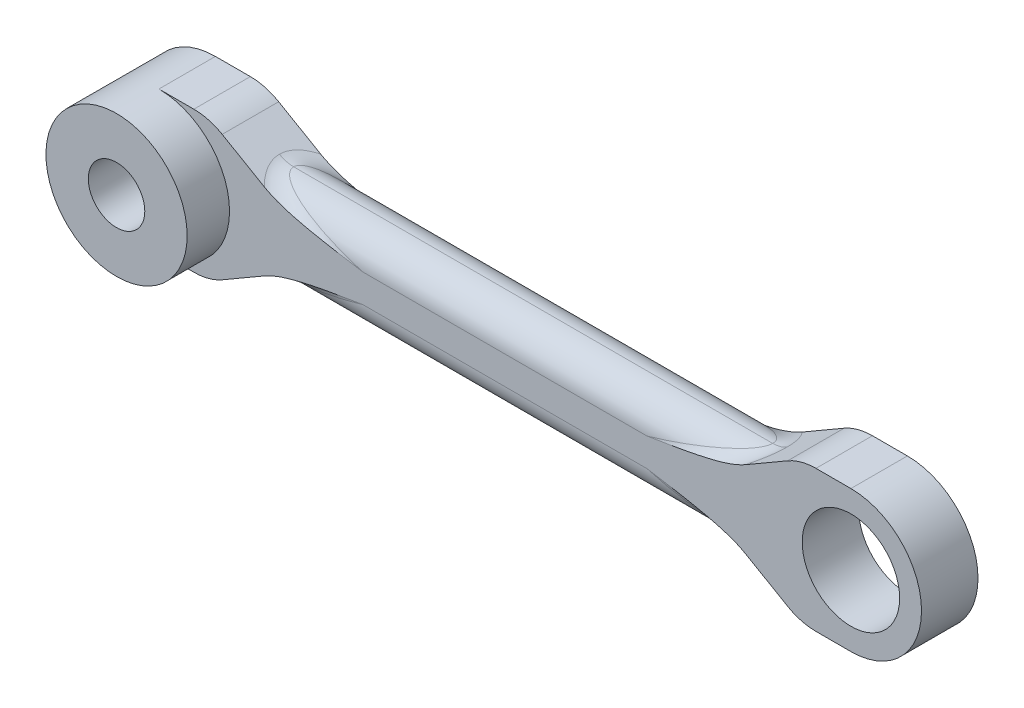
SolidWorks part; units mm, degrees
ref_plane "Ön Düzlem" through (0, 0, 0) normal (0, 0, 1) x (1, 0, 0)
ref_plane "Üst Düzlem" through (0, 0, 0) normal (0, 1, 0) x (1, 0, 0)
ref_plane "Sağ Düzlem" through (0, 0, 0) normal (1, 0, 0) x (0, 0, -1)
sketch "Çizim1" plane through (0, 0, 0) normal (0, 0, 1) x (1, 0, 0)
  line L0 (0, 5) -> (49, 5)
  line L1 (0, -5) -> (49, -5)
  circle A0 centre (0, 0) radius 5
  circle A1 centre (0, 0) radius 3.45
  circle A2 centre (49, 0) radius 3.45
  circle A3 centre (49, 0) radius 5
  dimension "D1" = 10
  dimension "D2" = 49
  dimension "D3" = 6.9
  dimension "D4" = 6.9
extrude "Yükseklik-Ekstrüzyon1" add sketch "Çizim1" along normal blind 4 contours A0 A1 | A3 L0 A0 L1 | A3 A2
sketch "Çizim2" plane through (0, 0, 4) normal (0, 0, 1) x (1, 0, 0)
  circle A0 centre (0, 0) radius 4
  circle A1 centre (0, 0) radius 1.5
extrude "Yükseklik-Ekstrüzyon2" add sketch "Çizim2" along normal blind 3
sketch "Çizim3" plane through (0, 0, 4) normal (0, 0, 1) x (1, 0, 0)
  circle A0 centre (0, 0) radius 5
extrude "Yükseklik-Ekstrüzyon3" add sketch "Çizim3" along normal blind 3
sketch "Çizim5" plane through (0, 0, 7) normal (0, 0, 1) x (1, 0, 0)
  circle A0 centre (0, 0) radius 2
  dimension "D1" = 4
extrude "Kes-Ekstrüzyon2" cut sketch "Çizim5" against normal blind 3
sketch "Çizim6" plane through (0, 0, 0) normal (0, 0, -1) x (-1, 0, 0)
  line L0 (-45.45, 5) -> (-42, 0)
  line L1 (0, 5) -> (-49, 5) construction
  line L2 (-42, 0) -> (-45.45, -5)
  line L3 (0, -5) -> (-49, -5) construction
  line L4 (-3.55, 5) -> (-7, 0)
  line L5 (-7, 0) -> (-3.55, -5)
  line L6 (-42, 0) -> (-7, 0)
  line L7 (-45.45, 5) -> (-42, 3)
  line L8 (-42, 3) -> (-7, 3)
  line L9 (-7, 3) -> (-3.55, 5)
  line L10 (-7, -3) -> (-3.55, -5)
  line L11 (-45.45, -5) -> (-42, -3)
  line L12 (-42, -3) -> (-7, -3)
  line L13 (-45.45, 5) -> (-3.55, 5)
  line L14 (-45.45, -5) -> (-3.55, -5)
  circle A0 centre (-49, 0) radius 3.45 construction
  line M7 (0, 5) -> (-49, 5)
  line M9 (-49, -5) -> (0, -5)
  dimension "D1" = 7
  dimension "D2" = 7
  dimension "D3" = 3
  dimension "D5" = 3.45
  dimension "D6" = 3.45
extrude "Kes-Ekstrüzyon3" cut sketch "Çizim6" against normal blind 10 contours L8 L9 L7 M7 | L12 L11 L10 M9
fillet "Radyus1" radius 2 4 edges at (24.5, -3, 4) (24.5, 3, 4) (24.5, -3, 0) (24.5, 3, 0)
fillet "Radyus2" radius 4 4 edges at (3.55, 5, 2) (3.55, -5, 2) (45.45, -5, 2) (45.45, 5, 2)
fillet "Radyus4" radius 2 8 edges at (40.9895, -2.4142, 3.4142) (8.0105, -2.4142, 3.4142) (8.0105, 2.4142, 3.4142) (40.9895, 2.4142, 3.4142) (40.9895, -2.4142, 0.5858) (8.0105, -2.4142, 0.5858) (8.0105, 2.4142, 0.5858) (40.9895, 2.4142, 0.5858)
